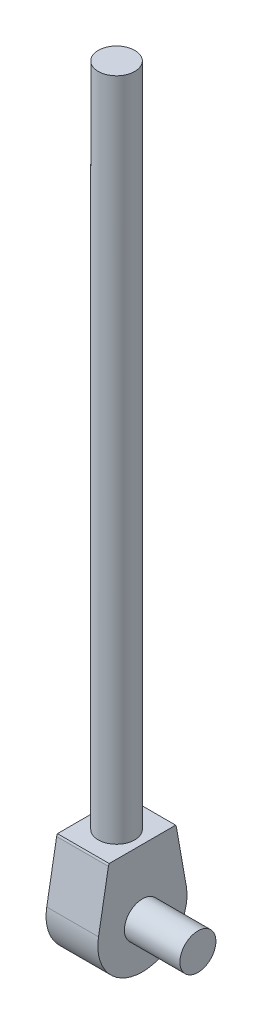
SolidWorks part; units mm, degrees
ref_plane "Front" through (0, 0, 0) normal (0, 0, 1) x (1, 0, 0)
ref_plane "Top" through (0, 0, 0) normal (0, 1, 0) x (1, 0, 0)
ref_plane "Right" through (0, 0, 0) normal (1, 0, 0) x (0, 0, -1)
sketch "Sketch6" plane through (0, 0, 0) normal (1, 0, 0) x (0, 0, -1)
  line L0 (36.5389, 71.6976) -> (-36.5389, 71.6976)
  line L1 (37.3703, 69.4136) -> (48.2503, 7.7362)
  line L3 (-37.3703, 69.4136) -> (-48.2503, 7.7362)
  arc A0 (37.3703, 69.4136) -> (36.5389, 71.6976) centre (30.4768, 68.1976) ccw
  arc A1 (-37.3703, 69.4136) -> (-36.5389, 71.6976) centre (-30.4767, 68.1976) cw
  arc A2 (48.2503, 7.7362) -> (-48.2503, 7.7362) centre (0, -0.7753) cw
extrude "Extrude1" add sketch "Sketch6" along normal blind 28.448 and the other way blind 28.448
sketch "Sketch7" plane through (0, 71.6976, 0) normal (0, 1, 0) x (-1, 0, 0)
  circle A0 centre (0, 0) radius 20.066
  dimension "D1" = 40.132
extrude "Extrude2" add sketch "Sketch7" along normal blind 731.393
sketch "Sketch8" plane through (28.448, 0, 0) normal (1, 0, 0) x (0, 0, -1)
  circle A0 centre (0, 0) radius 34.1738
extrude "Extrude3" add sketch "Sketch8" against normal blind 60.96
sketch "Sketch9" plane through (28.448, 0, 0) normal (1, 0, 0) x (0, 0, -1)
  circle A0 centre (0, 0) radius 19.812
  dimension "D1" = 39.624
extrude "Extrude4" add sketch "Sketch9" along normal blind 60.96
